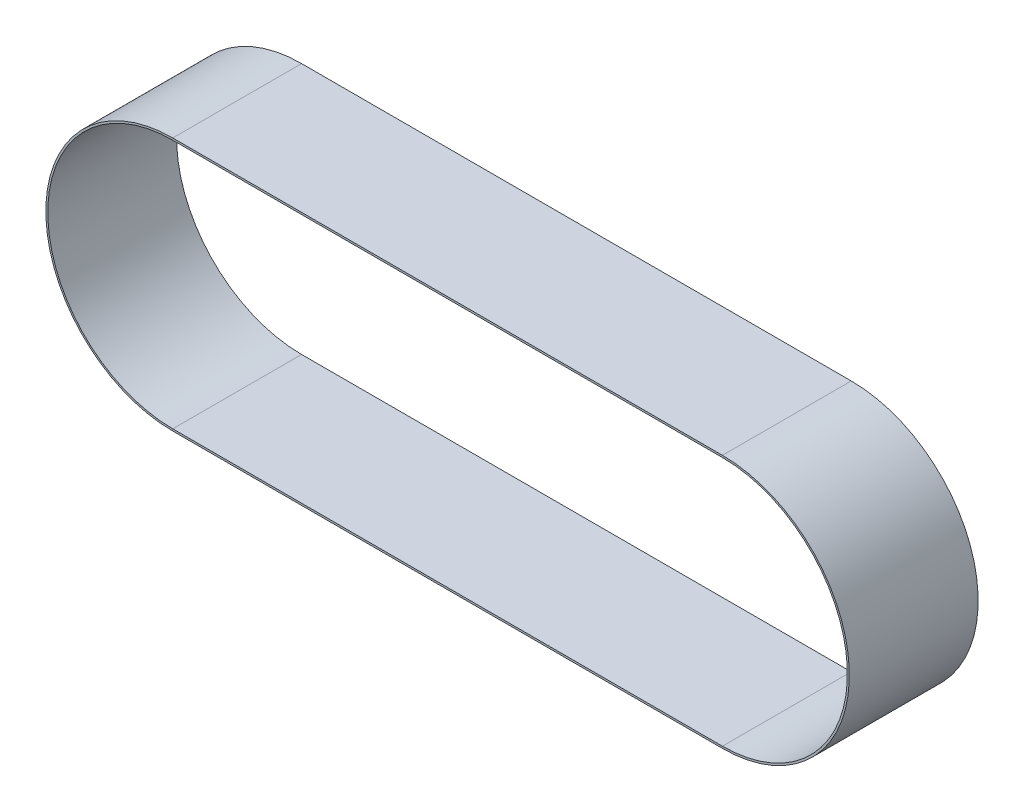
SolidWorks part; units mm, degrees
ref_plane "Front Plane" through (0, 0, 0) normal (0, 0, 1) x (1, 0, 0)
ref_plane "Top Plane" through (0, 0, 0) normal (0, 1, 0) x (1, 0, 0)
ref_plane "Right Plane" through (0, 0, 0) normal (1, 0, 0) x (0, 0, -1)
sketch "Sketch1" plane through (0, 0, 0) normal (0, 0, 1) x (1, 0, 0)
  line L0 (0, 29.105) -> (128, 29.105)
  line L1 (128, -29.105) -> (0, -29.105)
  line L2 (0, 29.555) -> (128, 29.555)
  line L3 (128, -29.555) -> (0, -29.555)
  circle A0 centre (0, 0) radius 29.105
  circle A1 centre (128, 0) radius 29.105
  circle A2 centre (0, 0) radius 29.555
  circle A3 centre (128, 0) radius 29.555
  dimension "D1" = 128
  dimension "D3" = 59.11
  dimension "D2" = 58.21
extrude "Boss-Extrude1" add sketch "Sketch1" along normal blind 30 contours L0 A2 L1 A0 | A3 L2 A2 L0 | A3 L0 A1 L1 | A3 L1 A2 L3 region at (-29.1735, 0, 0) region at (64, 29.3325, 0) region at (125.4272, 29.374, 0) region at (64, -29.3325, 0)
ref_axis "Axis1" through (0, 0, 30) along (0, 0, -1)
ref_axis "Axis2" through (128, 0, 30) along (0, 0, -1)
